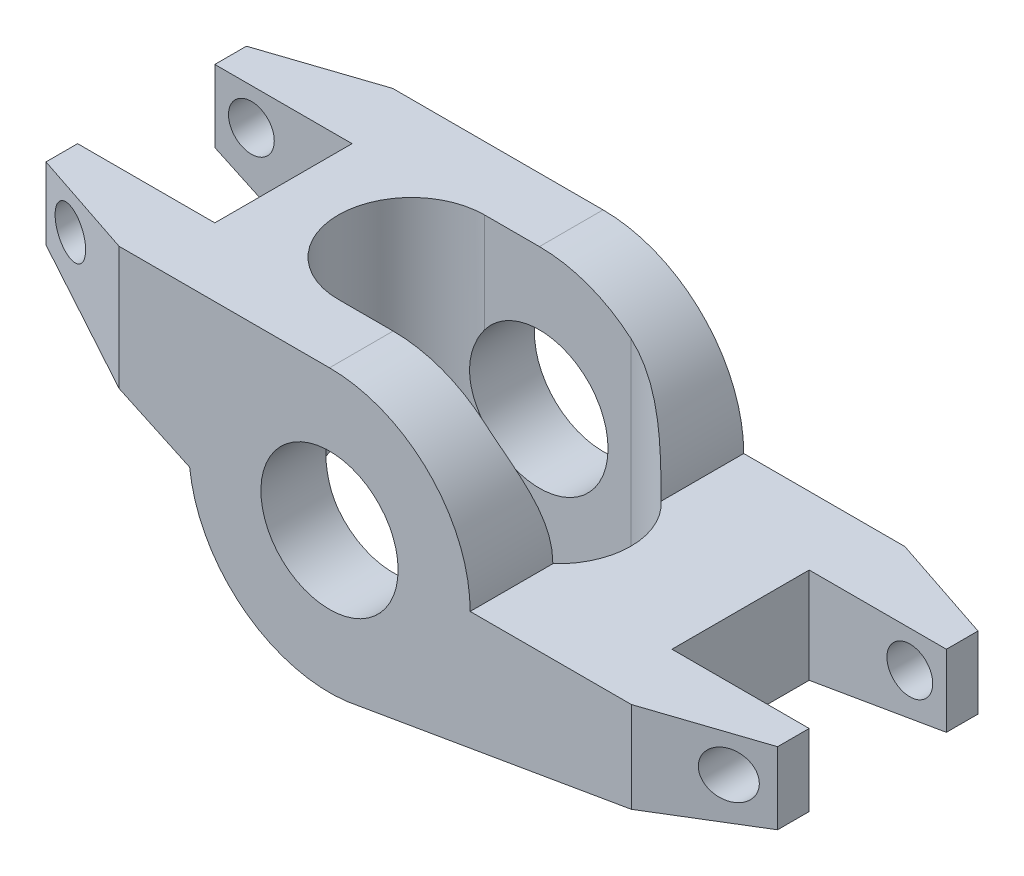
SolidWorks part; units mm, degrees
ref_plane "Front Plane" through (0, 0, 0) normal (0, 0, 1) x (1, 0, 0)
ref_plane "Top Plane" through (0, 0, 0) normal (0, 1, 0) x (1, 0, 0)
ref_plane "Right Plane" through (0, 0, 0) normal (1, 0, 0) x (0, 0, -1)
sketch "Sketch1" plane through (0, 0, 0) normal (0, 0, 1) x (1, 0, 0)
  line L0 (0, 9.77) -> (-22.23, 9.77)
  line L1 (-22.23, 9.77) -> (-22.23, 4.77)
  line L2 (-22.23, 4.77) -> (-9.7115, -1.0675)
  line L3 (9.77, 0) -> (28.58, 0)
  line L4 (28.58, 0) -> (28.58, -5)
  line L5 (28.58, -5) -> (2.103, -9.541)
  arc A0 (9.77, 0) -> (0, 9.77) centre (0, 0) ccw
  circle A1 centre (0, 0) radius 4.765
  arc A2 (-9.7115, -1.0675) -> (2.103, -9.541) centre (0, 0) ccw
  dimension "D1" = 19.54
  dimension "D2" = 9.53
  dimension "D3" = 5
  dimension "D4" = 25
  dimension "D5" = 22.23
  dimension "D6" = 28.58
extrude "Boss-Extrude1" add sketch "Sketch1" along normal mid plane 19
chamfer "Chamfer5" distance 7.62 distance2 2.54 2 edges at (28.58, -2.5, -9.5) (-22.23, 7.27, -9.5) first distance on face at (1.8744, 1.0113, -9.5)
chamfer "Chamfer6" distance 2.54 distance2 7.62 2 edges at (28.58, -2.5, 9.5) (-22.23, 7.27, 9.5) first distance on face at (28.58, -2.5, 1.27) first distance on face at (-22.23, 7.27, 1.27)
sketch "Sketch2" plane through (0, 0, 0) normal (0, 1, 0) x (1, 0, 0)
  line L0 (-22.23, -6.96) -> (-22.23, 6.96) construction
  line L1 (-22.23, 4.765) -> (-12.7, 4.765)
  line L2 (-22.23, 4.765) -> (-22.23, -4.765)
  line L3 (-22.23, -4.765) -> (-12.7, -4.765)
  line L4 (-12.7, 4.765) -> (-12.7, -4.765)
  line L5 (28.58, -6.96) -> (28.58, 6.96) construction
  line L6 (28.58, 4.765) -> (19.05, 4.765)
  line L7 (28.58, 4.765) -> (28.58, -4.765)
  line L8 (28.58, -4.765) -> (19.05, -4.765)
  line L9 (19.05, 4.765) -> (19.05, -4.765)
  point P12 (-22.23, 0)
  point P14 (19.05, 0)
  dimension "D1" = 9.53
extrude "Cut-Extrude1" cut sketch "Sketch2" against normal through all
extrude "Cut-Extrude2" cut sketch "Sketch2<2>" along normal through all
sketch "Sketch2<2>" plane through (0, 0, 0) normal (0, 1, 0) x (1, 0, 0) same geometry as "Sketch2"
sketch "Sketch3" plane through (0, 0, 0) normal (0, 1, 0) x (1, 0, 0)
  line L0 (-3.81, 0) -> (6.35, 0) construction
  line L1 (-3.81, 5.08) -> (6.35, 5.08)
  line L2 (-3.81, -5.08) -> (6.35, -5.08)
  line L3 (-12.7, -4.765) -> (-12.7, 4.765) construction
  arc A0 (-3.81, 5.08) -> (-3.81, -5.08) centre (-3.81, 0) ccw
  arc A1 (6.35, -5.08) -> (6.35, 5.08) centre (6.35, 0) ccw
  point P3 (1.27, 0)
  point P8 (0, 0)
  dimension "D2" = 5.08
  dimension "D1" = 8.89
  dimension "D3" = 10.16
extrude "Cut-Extrude3" cut sketch "Sketch3" against normal through all both and the other way through all
sketch "Sketch4" plane through (0, 0, 0) normal (0, 0, 1) x (1, 0, 0)
  line L0 (-22.23, 9.77) -> (-14.61, 9.77) construction
  line L1 (-22.23, 4.77) -> (-22.23, 9.77) construction
  line L2 (28.58, 0) -> (28.58, -5) construction
  line L3 (20.96, 0) -> (28.58, 0) construction
  circle A0 centre (-19.69, 7.23) radius 1.59
  circle A1 centre (26.04, -2.54) radius 1.59
  dimension "D5" = 3.18
  dimension "D6" = 3.18
  dimension "D1" = 2.54
  dimension "D2" = 2.54
  dimension "D3" = 2.54
  dimension "D4" = 2.54
extrude "Cut-Extrude4" cut sketch "Sketch4" against normal through all both and the other way through all
